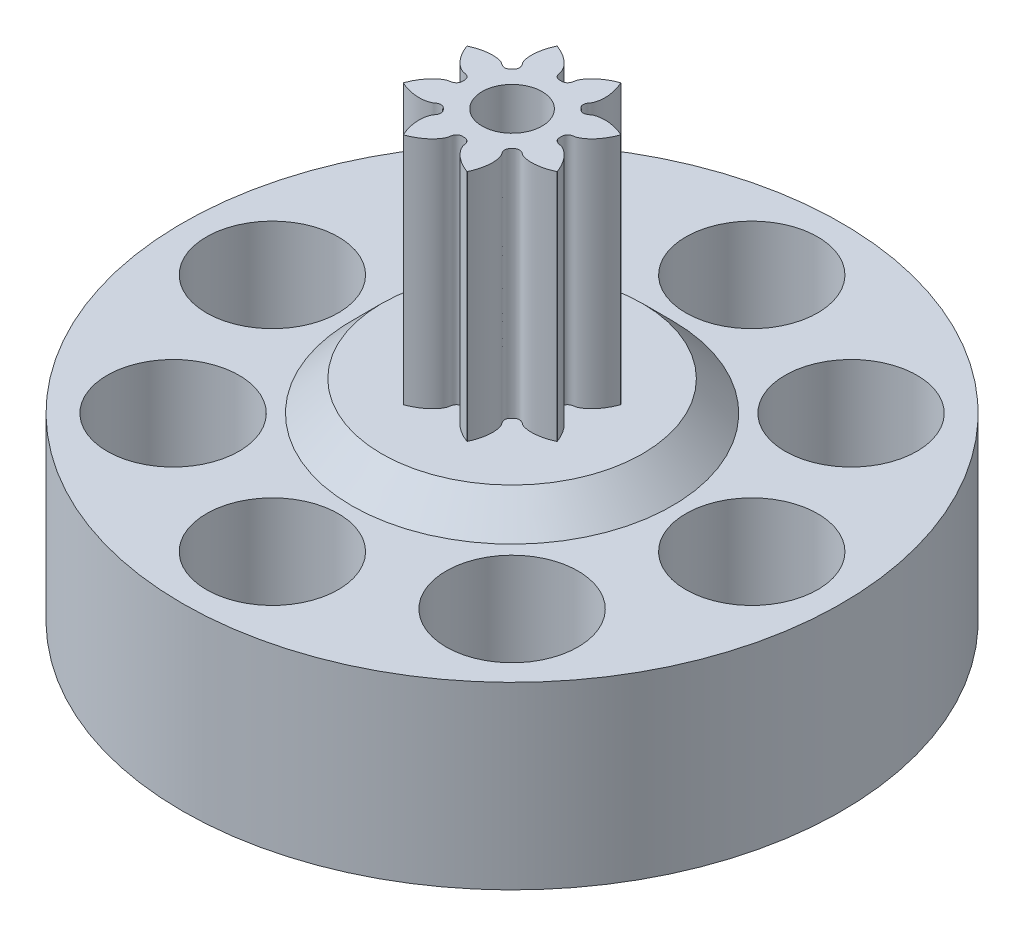
SolidWorks part; units mm, degrees
material "PLA"
ref_plane "Front Plane" through (0, 0, 0) normal (0, 0, 1) x (1, 0, 0)
ref_plane "Top Plane" through (0, 0, 0) normal (0, 1, 0) x (1, 0, 0)
ref_plane "Right Plane" through (0, 0, 0) normal (1, 0, 0) x (0, 0, -1)
sketch "Sketch1" plane through (0, 0, 0) normal (0, 1, 0) x (1, 0, 0)
  circle A0 centre (0, 0) radius 11
  dimension "D1" = 22
extrude "Boss-Extrude1" add sketch "Sketch1" along normal mid plane 6
sketch "Sketch2" plane through (0, 3, 0) normal (0, 1, 0) x (1, 0, 0)
  circle A0 centre (0, 8) radius 1
  circle A1 centre (-5.6569, 5.6569) radius 1
  circle A2 centre (5.6569, 5.6569) radius 1
  circle A3 centre (-5.6569, -5.6569) radius 1
  circle A4 centre (5.6569, -5.6569) radius 1
  circle A5 centre (-8, 0) radius 1
  circle A6 centre (0, -8) radius 1
  circle A7 centre (8, 0) radius 1
  circle A8 centre (0, 0) radius 4
  circle A9 centre (0, 0) radius 11
sketch "Sketch5" plane through (0, 3, 0) normal (0, 1, 0) x (1, 0, 0)
  line L0 (2.5656, 1.0576) -> (2.562, 1.0663)
  line L1 (1.0663, 2.562) -> (1.0576, 2.5656)
  line L2 (-1.0576, 2.5656) -> (-1.0663, 2.562)
  line L3 (-2.562, 1.0663) -> (-2.5656, 1.0576)
  line L4 (-2.5656, -1.0576) -> (-2.562, -1.0663)
  line L5 (-1.0663, -2.562) -> (-1.0576, -2.5656)
  line L6 (1.0576, -2.5656) -> (1.0663, -2.562)
  line L7 (2.562, -1.0663) -> (2.5656, -1.0576)
  circle A0 centre (0, 0) radius 1
  circle A1 centre (0, 0) radius 2.8
  spline S0 degree 3 poles (2.5656, 1.0576) (2.5467, 1.0063) (2.5127, 0.9243) (2.4586, 0.8162) (2.4108, 0.7326) (2.3616, 0.6567) (2.3117, 0.5883) (2.2618, 0.5274) (2.2125, 0.4736) (2.1645, 0.4267) (2.1184, 0.3865) (2.0746, 0.3524) (2.0339, 0.3241) (1.9966, 0.3012) (1.9632, 0.2831) (1.9342, 0.2695) (1.9099, 0.2596) (1.8905, 0.253) (1.8694, 0.2467) (1.8487, 0.2452) (1.828, 0.2423) (1.8074, 0.2387) (1.7821, 0.2325) (1.7521, 0.2221) (1.7278, 0.2103) (1.7086, 0.1983) (1.6939, 0.1875) (1.6793, 0.1746) (1.665, 0.1592) (1.6515, 0.1408) (1.6395, 0.1191) (1.6301, 0.0941) (1.6246, 0.0677) (1.6231, 0.036) (1.6249, 0) (1.6231, -0.036) (1.6246, -0.0677) (1.6301, -0.0941) (1.6395, -0.1191) (1.6515, -0.1408) (1.665, -0.1592) (1.6793, -0.1746) (1.6982, -0.1913) (1.7224, -0.2076) (1.7521, -0.2221) (1.7821, -0.2325) (1.8074, -0.2387) (1.828, -0.2423) (1.8487, -0.2452) (1.8694, -0.2467) (1.8905, -0.253) (1.9099, -0.2596) (1.9342, -0.2695) (1.9632, -0.2831) (1.9966, -0.3012) (2.0339, -0.3241) (2.0746, -0.3524) (2.1184, -0.3865) (2.1645, -0.4267) (2.2125, -0.4736) (2.2618, -0.5274) (2.3117, -0.5883) (2.3616, -0.6567) (2.4108, -0.7326) (2.4586, -0.8162) (2.5127, -0.9243) (2.5467, -1.0063) (2.5656, -1.0576) knots 0.018496 0.018496 0.018496 0.018496 0.071158 0.103928 0.134826 0.16385 0.191003 0.216283 0.23969 0.261224 0.280886 0.298676 0.314593 0.328637 0.340809 0.351108 0.359535 0.366089 0.37077 0.380767 0.385886 0.390938 0.400931 0.410975 0.421412 0.426928 0.432746 0.438959 0.445665 0.452957 0.460893 0.469469 0.478579 0.486756 0.5 0.513244 0.521421 0.530531 0.539107 0.547043 0.554335 0.561041 0.567254 0.578588 0.589025 0.599069 0.609062 0.614114 0.619233 0.62923 0.633911 0.640465 0.648892 0.659191 0.671363 0.685407 0.701324 0.719114 0.738776 0.76031 0.783717 0.808997 0.83615 0.865174 0.896072 0.928842 0.981504 0.981504 0.981504 0.981504
  spline S1 degree 3 poles (1.0663, 2.562) (1.0892, 2.5123) (1.1232, 2.4303) (1.1614, 2.3156) (1.1867, 2.2227) (1.2056, 2.1343) (1.2186, 2.0507) (1.2264, 1.9723) (1.2296, 1.8994) (1.2288, 1.8323) (1.2246, 1.7712) (1.2178, 1.7162) (1.209, 1.6673) (1.1988, 1.6248) (1.188, 1.5884) (1.1771, 1.5582) (1.1669, 1.534) (1.1579, 1.5157) (1.1474, 1.4963) (1.1339, 1.4806) (1.1212, 1.464) (1.1092, 1.4468) (1.0957, 1.4245) (1.0819, 1.396) (1.0731, 1.3704) (1.0679, 1.3484) (1.0652, 1.3304) (1.0639, 1.3109) (1.0647, 1.2899) (1.0682, 1.2673) (1.0751, 1.2435) (1.0861, 1.2192) (1.1009, 1.1966) (1.1223, 1.1732) (1.149, 1.149) (1.1732, 1.1223) (1.1966, 1.1009) (1.2192, 1.0861) (1.2435, 1.0751) (1.2673, 1.0682) (1.2899, 1.0647) (1.3109, 1.0639) (1.3361, 1.0655) (1.3647, 1.0711) (1.396, 1.0819) (1.4245, 1.0957) (1.4468, 1.1092) (1.464, 1.1212) (1.4806, 1.1339) (1.4963, 1.1474) (1.5157, 1.1579) (1.534, 1.1669) (1.5582, 1.1771) (1.5884, 1.188) (1.6248, 1.1988) (1.6673, 1.209) (1.7162, 1.2178) (1.7712, 1.2246) (1.8323, 1.2288) (1.8994, 1.2296) (1.9723, 1.2264) (2.0507, 1.2186) (2.1343, 1.2056) (2.2227, 1.1867) (2.3156, 1.1614) (2.4303, 1.1232) (2.5123, 1.0892) (2.562, 1.0663) knots 0.018496 0.018496 0.018496 0.018496 0.071158 0.103928 0.134826 0.16385 0.191003 0.216283 0.23969 0.261224 0.280886 0.298676 0.314593 0.328637 0.340809 0.351108 0.359535 0.366089 0.37077 0.380767 0.385886 0.390938 0.400931 0.410975 0.421412 0.426928 0.432746 0.438959 0.445665 0.452957 0.460893 0.469469 0.478579 0.486756 0.5 0.513244 0.521421 0.530531 0.539107 0.547043 0.554335 0.561041 0.567254 0.578588 0.589025 0.599069 0.609062 0.614114 0.619233 0.62923 0.633911 0.640465 0.648892 0.659191 0.671363 0.685407 0.701324 0.719114 0.738776 0.76031 0.783717 0.808997 0.83615 0.865174 0.896072 0.928842 0.981504 0.981504 0.981504 0.981504
  spline S2 degree 3 poles (-1.0576, 2.5656) (-1.0063, 2.5467) (-0.9243, 2.5127) (-0.8162, 2.4586) (-0.7326, 2.4108) (-0.6567, 2.3616) (-0.5883, 2.3117) (-0.5274, 2.2618) (-0.4736, 2.2125) (-0.4267, 2.1645) (-0.3865, 2.1184) (-0.3524, 2.0746) (-0.3241, 2.0339) (-0.3012, 1.9966) (-0.2831, 1.9632) (-0.2695, 1.9342) (-0.2596, 1.9099) (-0.253, 1.8905) (-0.2467, 1.8694) (-0.2452, 1.8487) (-0.2423, 1.828) (-0.2387, 1.8074) (-0.2325, 1.7821) (-0.2221, 1.7521) (-0.2103, 1.7278) (-0.1983, 1.7086) (-0.1875, 1.6939) (-0.1746, 1.6793) (-0.1592, 1.665) (-0.1408, 1.6515) (-0.1191, 1.6395) (-0.0941, 1.6301) (-0.0677, 1.6246) (-0.036, 1.6231) (0, 1.6249) (0.036, 1.6231) (0.0677, 1.6246) (0.0941, 1.6301) (0.1191, 1.6395) (0.1408, 1.6515) (0.1592, 1.665) (0.1746, 1.6793) (0.1913, 1.6982) (0.2076, 1.7224) (0.2221, 1.7521) (0.2325, 1.7821) (0.2387, 1.8074) (0.2423, 1.828) (0.2452, 1.8487) (0.2467, 1.8694) (0.253, 1.8905) (0.2596, 1.9099) (0.2695, 1.9342) (0.2831, 1.9632) (0.3012, 1.9966) (0.3241, 2.0339) (0.3524, 2.0746) (0.3865, 2.1184) (0.4267, 2.1645) (0.4736, 2.2125) (0.5274, 2.2618) (0.5883, 2.3117) (0.6567, 2.3616) (0.7326, 2.4108) (0.8162, 2.4586) (0.9243, 2.5127) (1.0063, 2.5467) (1.0576, 2.5656) knots 0.018496 0.018496 0.018496 0.018496 0.071158 0.103928 0.134826 0.16385 0.191003 0.216283 0.23969 0.261224 0.280886 0.298676 0.314593 0.328637 0.340809 0.351108 0.359535 0.366089 0.37077 0.380767 0.385886 0.390938 0.400931 0.410975 0.421412 0.426928 0.432746 0.438959 0.445665 0.452957 0.460893 0.469469 0.478579 0.486756 0.5 0.513244 0.521421 0.530531 0.539107 0.547043 0.554335 0.561041 0.567254 0.578588 0.589025 0.599069 0.609062 0.614114 0.619233 0.62923 0.633911 0.640465 0.648892 0.659191 0.671363 0.685407 0.701324 0.719114 0.738776 0.76031 0.783717 0.808997 0.83615 0.865174 0.896072 0.928842 0.981504 0.981504 0.981504 0.981504
  spline S3 degree 3 poles (-2.562, 1.0663) (-2.5123, 1.0892) (-2.4303, 1.1232) (-2.3156, 1.1614) (-2.2227, 1.1867) (-2.1343, 1.2056) (-2.0507, 1.2186) (-1.9723, 1.2264) (-1.8994, 1.2296) (-1.8323, 1.2288) (-1.7712, 1.2246) (-1.7162, 1.2178) (-1.6673, 1.209) (-1.6248, 1.1988) (-1.5884, 1.188) (-1.5582, 1.1771) (-1.534, 1.1669) (-1.5157, 1.1579) (-1.4963, 1.1474) (-1.4806, 1.1339) (-1.464, 1.1212) (-1.4468, 1.1092) (-1.4245, 1.0957) (-1.396, 1.0819) (-1.3704, 1.0731) (-1.3484, 1.0679) (-1.3304, 1.0652) (-1.3109, 1.0639) (-1.2899, 1.0647) (-1.2673, 1.0682) (-1.2435, 1.0751) (-1.2192, 1.0861) (-1.1966, 1.1009) (-1.1732, 1.1223) (-1.149, 1.149) (-1.1223, 1.1732) (-1.1009, 1.1966) (-1.0861, 1.2192) (-1.0751, 1.2435) (-1.0682, 1.2673) (-1.0647, 1.2899) (-1.0639, 1.3109) (-1.0655, 1.3361) (-1.0711, 1.3647) (-1.0819, 1.396) (-1.0957, 1.4245) (-1.1092, 1.4468) (-1.1212, 1.464) (-1.1339, 1.4806) (-1.1474, 1.4963) (-1.1579, 1.5157) (-1.1669, 1.534) (-1.1771, 1.5582) (-1.188, 1.5884) (-1.1988, 1.6248) (-1.209, 1.6673) (-1.2178, 1.7162) (-1.2246, 1.7712) (-1.2288, 1.8323) (-1.2296, 1.8994) (-1.2264, 1.9723) (-1.2186, 2.0507) (-1.2056, 2.1343) (-1.1867, 2.2227) (-1.1614, 2.3156) (-1.1232, 2.4303) (-1.0892, 2.5123) (-1.0663, 2.562) knots 0.018496 0.018496 0.018496 0.018496 0.071158 0.103928 0.134826 0.16385 0.191003 0.216283 0.23969 0.261224 0.280886 0.298676 0.314593 0.328637 0.340809 0.351108 0.359535 0.366089 0.37077 0.380767 0.385886 0.390938 0.400931 0.410975 0.421412 0.426928 0.432746 0.438959 0.445665 0.452957 0.460893 0.469469 0.478579 0.486756 0.5 0.513244 0.521421 0.530531 0.539107 0.547043 0.554335 0.561041 0.567254 0.578588 0.589025 0.599069 0.609062 0.614114 0.619233 0.62923 0.633911 0.640465 0.648892 0.659191 0.671363 0.685407 0.701324 0.719114 0.738776 0.76031 0.783717 0.808997 0.83615 0.865174 0.896072 0.928842 0.981504 0.981504 0.981504 0.981504
  spline S4 degree 3 poles (-2.5656, -1.0576) (-2.5467, -1.0063) (-2.5127, -0.9243) (-2.4586, -0.8162) (-2.4108, -0.7326) (-2.3616, -0.6567) (-2.3117, -0.5883) (-2.2618, -0.5274) (-2.2125, -0.4736) (-2.1645, -0.4267) (-2.1184, -0.3865) (-2.0746, -0.3524) (-2.0339, -0.3241) (-1.9966, -0.3012) (-1.9632, -0.2831) (-1.9342, -0.2695) (-1.9099, -0.2596) (-1.8905, -0.253) (-1.8694, -0.2467) (-1.8487, -0.2452) (-1.828, -0.2423) (-1.8074, -0.2387) (-1.7821, -0.2325) (-1.7521, -0.2221) (-1.7278, -0.2103) (-1.7086, -0.1983) (-1.6939, -0.1875) (-1.6793, -0.1746) (-1.665, -0.1592) (-1.6515, -0.1408) (-1.6395, -0.1191) (-1.6301, -0.0941) (-1.6246, -0.0677) (-1.6231, -0.036) (-1.6249, 0) (-1.6231, 0.036) (-1.6246, 0.0677) (-1.6301, 0.0941) (-1.6395, 0.1191) (-1.6515, 0.1408) (-1.665, 0.1592) (-1.6793, 0.1746) (-1.6982, 0.1913) (-1.7224, 0.2076) (-1.7521, 0.2221) (-1.7821, 0.2325) (-1.8074, 0.2387) (-1.828, 0.2423) (-1.8487, 0.2452) (-1.8694, 0.2467) (-1.8905, 0.253) (-1.9099, 0.2596) (-1.9342, 0.2695) (-1.9632, 0.2831) (-1.9966, 0.3012) (-2.0339, 0.3241) (-2.0746, 0.3524) (-2.1184, 0.3865) (-2.1645, 0.4267) (-2.2125, 0.4736) (-2.2618, 0.5274) (-2.3117, 0.5883) (-2.3616, 0.6567) (-2.4108, 0.7326) (-2.4586, 0.8162) (-2.5127, 0.9243) (-2.5467, 1.0063) (-2.5656, 1.0576) knots 0.018496 0.018496 0.018496 0.018496 0.071158 0.103928 0.134826 0.16385 0.191003 0.216283 0.23969 0.261224 0.280886 0.298676 0.314593 0.328637 0.340809 0.351108 0.359535 0.366089 0.37077 0.380767 0.385886 0.390938 0.400931 0.410975 0.421412 0.426928 0.432746 0.438959 0.445665 0.452957 0.460893 0.469469 0.478579 0.486756 0.5 0.513244 0.521421 0.530531 0.539107 0.547043 0.554335 0.561041 0.567254 0.578588 0.589025 0.599069 0.609062 0.614114 0.619233 0.62923 0.633911 0.640465 0.648892 0.659191 0.671363 0.685407 0.701324 0.719114 0.738776 0.76031 0.783717 0.808997 0.83615 0.865174 0.896072 0.928842 0.981504 0.981504 0.981504 0.981504
  spline S5 degree 3 poles (-1.0663, -2.562) (-1.0892, -2.5123) (-1.1232, -2.4303) (-1.1614, -2.3156) (-1.1867, -2.2227) (-1.2056, -2.1343) (-1.2186, -2.0507) (-1.2264, -1.9723) (-1.2296, -1.8994) (-1.2288, -1.8323) (-1.2246, -1.7712) (-1.2178, -1.7162) (-1.209, -1.6673) (-1.1988, -1.6248) (-1.188, -1.5884) (-1.1771, -1.5582) (-1.1669, -1.534) (-1.1579, -1.5157) (-1.1474, -1.4963) (-1.1339, -1.4806) (-1.1212, -1.464) (-1.1092, -1.4468) (-1.0957, -1.4245) (-1.0819, -1.396) (-1.0731, -1.3704) (-1.0679, -1.3484) (-1.0652, -1.3304) (-1.0639, -1.3109) (-1.0647, -1.2899) (-1.0682, -1.2673) (-1.0751, -1.2435) (-1.0861, -1.2192) (-1.1009, -1.1966) (-1.1223, -1.1732) (-1.149, -1.149) (-1.1732, -1.1223) (-1.1966, -1.1009) (-1.2192, -1.0861) (-1.2435, -1.0751) (-1.2673, -1.0682) (-1.2899, -1.0647) (-1.3109, -1.0639) (-1.3361, -1.0655) (-1.3647, -1.0711) (-1.396, -1.0819) (-1.4245, -1.0957) (-1.4468, -1.1092) (-1.464, -1.1212) (-1.4806, -1.1339) (-1.4963, -1.1474) (-1.5157, -1.1579) (-1.534, -1.1669) (-1.5582, -1.1771) (-1.5884, -1.188) (-1.6248, -1.1988) (-1.6673, -1.209) (-1.7162, -1.2178) (-1.7712, -1.2246) (-1.8323, -1.2288) (-1.8994, -1.2296) (-1.9723, -1.2264) (-2.0507, -1.2186) (-2.1343, -1.2056) (-2.2227, -1.1867) (-2.3156, -1.1614) (-2.4303, -1.1232) (-2.5123, -1.0892) (-2.562, -1.0663) knots 0.018496 0.018496 0.018496 0.018496 0.071158 0.103928 0.134826 0.16385 0.191003 0.216283 0.23969 0.261224 0.280886 0.298676 0.314593 0.328637 0.340809 0.351108 0.359535 0.366089 0.37077 0.380767 0.385886 0.390938 0.400931 0.410975 0.421412 0.426928 0.432746 0.438959 0.445665 0.452957 0.460893 0.469469 0.478579 0.486756 0.5 0.513244 0.521421 0.530531 0.539107 0.547043 0.554335 0.561041 0.567254 0.578588 0.589025 0.599069 0.609062 0.614114 0.619233 0.62923 0.633911 0.640465 0.648892 0.659191 0.671363 0.685407 0.701324 0.719114 0.738776 0.76031 0.783717 0.808997 0.83615 0.865174 0.896072 0.928842 0.981504 0.981504 0.981504 0.981504
  spline S6 degree 3 poles (1.0576, -2.5656) (1.0063, -2.5467) (0.9243, -2.5127) (0.8162, -2.4586) (0.7326, -2.4108) (0.6567, -2.3616) (0.5883, -2.3117) (0.5274, -2.2618) (0.4736, -2.2125) (0.4267, -2.1645) (0.3865, -2.1184) (0.3524, -2.0746) (0.3241, -2.0339) (0.3012, -1.9966) (0.2831, -1.9632) (0.2695, -1.9342) (0.2596, -1.9099) (0.253, -1.8905) (0.2467, -1.8694) (0.2452, -1.8487) (0.2423, -1.828) (0.2387, -1.8074) (0.2325, -1.7821) (0.2221, -1.7521) (0.2103, -1.7278) (0.1983, -1.7086) (0.1875, -1.6939) (0.1746, -1.6793) (0.1592, -1.665) (0.1408, -1.6515) (0.1191, -1.6395) (0.0941, -1.6301) (0.0677, -1.6246) (0.036, -1.6231) (0, -1.6249) (-0.036, -1.6231) (-0.0677, -1.6246) (-0.0941, -1.6301) (-0.1191, -1.6395) (-0.1408, -1.6515) (-0.1592, -1.665) (-0.1746, -1.6793) (-0.1913, -1.6982) (-0.2076, -1.7224) (-0.2221, -1.7521) (-0.2325, -1.7821) (-0.2387, -1.8074) (-0.2423, -1.828) (-0.2452, -1.8487) (-0.2467, -1.8694) (-0.253, -1.8905) (-0.2596, -1.9099) (-0.2695, -1.9342) (-0.2831, -1.9632) (-0.3012, -1.9966) (-0.3241, -2.0339) (-0.3524, -2.0746) (-0.3865, -2.1184) (-0.4267, -2.1645) (-0.4736, -2.2125) (-0.5274, -2.2618) (-0.5883, -2.3117) (-0.6567, -2.3616) (-0.7326, -2.4108) (-0.8162, -2.4586) (-0.9243, -2.5127) (-1.0063, -2.5467) (-1.0576, -2.5656) knots 0.018496 0.018496 0.018496 0.018496 0.071158 0.103928 0.134826 0.16385 0.191003 0.216283 0.23969 0.261224 0.280886 0.298676 0.314593 0.328637 0.340809 0.351108 0.359535 0.366089 0.37077 0.380767 0.385886 0.390938 0.400931 0.410975 0.421412 0.426928 0.432746 0.438959 0.445665 0.452957 0.460893 0.469469 0.478579 0.486756 0.5 0.513244 0.521421 0.530531 0.539107 0.547043 0.554335 0.561041 0.567254 0.578588 0.589025 0.599069 0.609062 0.614114 0.619233 0.62923 0.633911 0.640465 0.648892 0.659191 0.671363 0.685407 0.701324 0.719114 0.738776 0.76031 0.783717 0.808997 0.83615 0.865174 0.896072 0.928842 0.981504 0.981504 0.981504 0.981504
  spline S7 degree 3 poles (2.562, -1.0663) (2.5123, -1.0892) (2.4303, -1.1232) (2.3156, -1.1614) (2.2227, -1.1867) (2.1343, -1.2056) (2.0507, -1.2186) (1.9723, -1.2264) (1.8994, -1.2296) (1.8323, -1.2288) (1.7712, -1.2246) (1.7162, -1.2178) (1.6673, -1.209) (1.6248, -1.1988) (1.5884, -1.188) (1.5582, -1.1771) (1.534, -1.1669) (1.5157, -1.1579) (1.4963, -1.1474) (1.4806, -1.1339) (1.464, -1.1212) (1.4468, -1.1092) (1.4245, -1.0957) (1.396, -1.0819) (1.3704, -1.0731) (1.3484, -1.0679) (1.3304, -1.0652) (1.3109, -1.0639) (1.2899, -1.0647) (1.2673, -1.0682) (1.2435, -1.0751) (1.2192, -1.0861) (1.1966, -1.1009) (1.1732, -1.1223) (1.149, -1.149) (1.1223, -1.1732) (1.1009, -1.1966) (1.0861, -1.2192) (1.0751, -1.2435) (1.0682, -1.2673) (1.0647, -1.2899) (1.0639, -1.3109) (1.0655, -1.3361) (1.0711, -1.3647) (1.0819, -1.396) (1.0957, -1.4245) (1.1092, -1.4468) (1.1212, -1.464) (1.1339, -1.4806) (1.1474, -1.4963) (1.1579, -1.5157) (1.1669, -1.534) (1.1771, -1.5582) (1.188, -1.5884) (1.1988, -1.6248) (1.209, -1.6673) (1.2178, -1.7162) (1.2246, -1.7712) (1.2288, -1.8323) (1.2296, -1.8994) (1.2264, -1.9723) (1.2186, -2.0507) (1.2056, -2.1343) (1.1867, -2.2227) (1.1614, -2.3156) (1.1232, -2.4303) (1.0892, -2.5123) (1.0663, -2.562) knots 0.018496 0.018496 0.018496 0.018496 0.071158 0.103928 0.134826 0.16385 0.191003 0.216283 0.23969 0.261224 0.280886 0.298676 0.314593 0.328637 0.340809 0.351108 0.359535 0.366089 0.37077 0.380767 0.385886 0.390938 0.400931 0.410975 0.421412 0.426928 0.432746 0.438959 0.445665 0.452957 0.460893 0.469469 0.478579 0.486756 0.5 0.513244 0.521421 0.530531 0.539107 0.547043 0.554335 0.561041 0.567254 0.578588 0.589025 0.599069 0.609062 0.614114 0.619233 0.62923 0.633911 0.640465 0.648892 0.659191 0.671363 0.685407 0.701324 0.719114 0.738776 0.76031 0.783717 0.808997 0.83615 0.865174 0.896072 0.928842 0.981504 0.981504 0.981504 0.981504
  dimension "D1" = 2
  dimension "D2" = 5.6
extrude "Boss-Extrude2" add sketch "Sketch5" along normal blind 8.8 contours S7 L7 S0 L0 S1 L1 S2 L2 S3 L3 S4 L4 S5 L5 S6 L6 A0 region at (1.5516, 3, 0)
hole_wizard "CBORE for M2 SHCS3" positions "Sketch11" profile "Sketch13" counterbore size "M2" standard "ANSI Metric"
sketch "Sketch11" plane through (0, 3, 0) normal (0, 1, 0) x (1, 0, 0)
  point P0 (-8, 0)
  point P3 (-5.6569, 5.6569)
  point P6 (0, 8)
  point P9 (5.6569, 5.6569)
  point P12 (8, 0)
  point P15 (5.6569, -5.6569)
  point P18 (0, -8)
  point P21 (-5.6569, -5.6569)
sketch "Sketch13" plane through (-8, 3, 0) normal (1, 0, 0) x (0, 0, 1)
  line L0 (0, 0) -> (0, 6.7811)
  line L1 (0, 6.7811) -> (1.3, 6)
  line L2 (1.3, 6) -> (1.3, 5)
  line L3 (1.3, 5) -> (2.2, 5)
  line L4 (2.2, 5) -> (2.2, 0)
  line L5 (2.2, 0) -> (0, 0)
  line L10 (0, 6.7811) -> (-1.3, 6) construction
  line L11 (0, -6.35) -> (0, 107.95) construction
  dimension "Hole Dia." = 2.6
  dimension "Hole Depth" = 6
  dimension "C'Bore Dia." = 4.4
  dimension "C'Bore Depth" = 5
  dimension "Drill Angle" = 118
sketch "Sketch14" plane through (0, -3, 0) normal (0, -1, 0) x (1, 0, 0)
  circle A0 centre (0, 0) radius 4.2
  dimension "D1" = 8.4
extrude "Cut-Extrude4" cut sketch "Sketch14" against normal blind 5.95
sketch "Sketch15" plane through (0, 3, 0) normal (0, 1, 0) x (1, 0, 0)
  circle A0 centre (0, 0) radius 4.35
  dimension "D1" = 8.7
extrude "Boss-Extrude4" add sketch "Sketch15" along normal blind 1
chamfer "Chamfer1" distance 1 angle 45 1 edges at (0, 3, 4.35)
